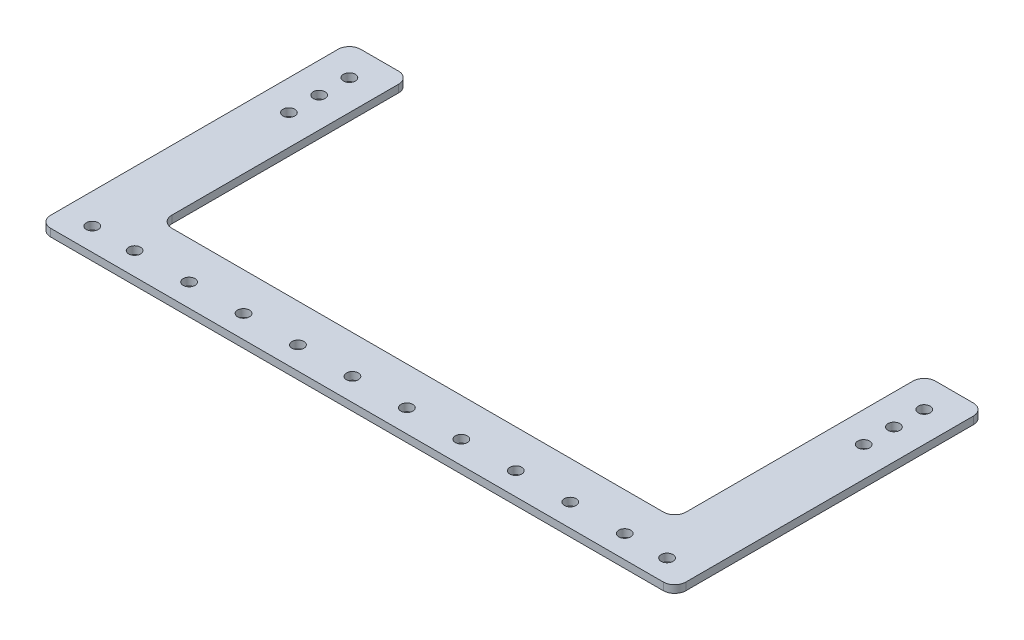
SolidWorks part; units mm, degrees
material "6061-T6 (SS)"
ref_plane "Front Plane" through (0, 0, 0) normal (0, 0, 1) x (1, 0, 0)
ref_plane "Top Plane" through (0, 0, 0) normal (0, 1, 0) x (1, 0, 0)
ref_plane "Right Plane" through (0, 0, 0) normal (1, 0, 0) x (0, 0, -1)
sketch "Sketch2" plane through (0, 0, 0) normal (0, 1, 0) x (1, 0, 0)
  line L0 (0, 65.0875) -> (0, -65.0875) construction
  line L1 (-133.35, -65.0875) -> (133.35, -65.0875)
  line L2 (-133.35, -65.0875) -> (-133.35, 65.0875)
  line L3 (-133.35, 65.0875) -> (133.35, 65.0875)
  line L4 (133.35, -65.0875) -> (133.35, 65.0875)
  line L5 (-133.35, -65.0875) -> (133.35, 65.0875) construction
  line L6 (-133.35, 65.0875) -> (133.35, -65.0875) construction
  line L7 (-107.95, 65.0875) -> (107.95, 65.0875)
  line L8 (-107.95, 65.0875) -> (-107.95, -39.624)
  line L9 (-107.95, -39.624) -> (107.95, -39.624)
  line L10 (107.95, 65.0875) -> (107.95, -39.624)
  line L11 (133.35, 65.0875) -> (107.95, 65.0875) construction
  line L12 (133.35, 65.0875) -> (133.35, -39.624) construction
  line L13 (133.35, -39.624) -> (107.95, -39.624) construction
  line L14 (107.95, 65.0875) -> (107.95, -39.624) construction
  circle A0 centre (-120.65, 52.3875) radius 2.4892
  circle A1 centre (-120.65, 39.6875) radius 2.4892
  circle A2 centre (-120.65, 26.9875) radius 2.4892
  circle A6 centre (120.65, 26.9875) radius 2.4892
  circle A7 centre (120.65, 39.6875) radius 2.4892
  circle A8 centre (120.65, 52.3875) radius 2.4892
  point P0 (0, 0)
  point P10 (0, -39.624)
  point P11 (0, -65.0875)
  dimension "D8" = 4.9784
  dimension "D1" = 266.7
  dimension "D2" = 130.175
  dimension "D3" = 215.9
  dimension "D4" = 25.4635
  dimension "D5" = 12.7
  dimension "D6" = 12.7
  dimension "D7" = 12.7
  dimension "D9" = 12.7
  dimension "D10" = 12.7
  dimension "D11" = 12.7
extrude "Boss-Extrude1" add sketch "Sketch2" along normal blind 3.175 contours L3 L10 L9 L8 L2 L1 L4 A7 A0 A1 A2 A6 A8 region at (-130.3823, 0, 0)
fillet "Fillet1" radius 4.7625 8 edges at (133.35, 1.5875, -65.0875) (-133.35, 1.5875, 65.0875) (-133.35, 1.5875, -65.0875) (-107.95, 1.5875, -65.0875) (-107.95, 1.5875, 39.624) (107.95, 1.5875, 39.624) (107.95, 1.5875, -65.0875) (133.35, 1.5875, 65.0875)
sketch "Sketch3" plane through (0, 3.175, 0) normal (0, 1, 0) x (1, 0, 0)
  line L0 (-133.35, -60.325) -> (-133.35, 60.325) construction
  line L1 (-128.5875, -65.0875) -> (128.5875, -65.0875) construction
  line L2 (102.87, -55.5625) -> (120.65, -55.5625) construction
  line L3 (-103.1875, -39.624) -> (103.1875, -39.624) construction
  line L4 (-44.45, -39.624) -> (-44.45, -65.0875) construction
  line L5 (-120.65, -55.5625) -> (-102.87, -55.5625) construction
  line L7 (-107.95, -39.624) -> (107.95, -39.624) construction
  line L8 (-48.4188, -39.624) -> (-40.4813, -39.624) construction
  line L9 (-48.4188, -39.624) -> (-48.4188, -65.0875) construction
  line L10 (-48.4188, -65.0875) -> (-40.4813, -65.0875) construction
  line L11 (-40.4813, -39.624) -> (-40.4813, -65.0875) construction
  line L12 (-133.35, -65.0875) -> (133.35, -65.0875) construction
  circle A38 centre (-102.87, -55.5625) radius 2.4892
  circle A40 centre (-80.01, -55.5625) radius 2.4892
  circle A41 centre (-120.65, -55.5625) radius 2.4892
  circle A55 centre (-57.15, -55.5625) radius 2.4892
  circle A63 centre (120.65, -55.5625) radius 2.4892
  circle A64 centre (-120.65, 26.9875) radius 2.4892 construction
  circle A65 centre (-34.29, -55.5625) radius 2.4892
  circle A66 centre (-11.43, -55.5625) radius 2.4892
  circle A67 centre (11.43, -55.5625) radius 2.4892
  circle A68 centre (34.29, -55.5625) radius 2.4892
  circle A69 centre (57.15, -55.5625) radius 2.4892
  circle A74 centre (80.01, -55.5625) radius 2.4892
  circle A75 centre (102.87, -55.5625) radius 2.4892
  point P48 (-44.45, -39.624)
  dimension "D1" = 22.86
  dimension "D6" = 88.9
  dimension "D2" = 12.7
  dimension "D3" = 9.525
  dimension "D4" = 10
  dimension "D7" = 7.9375
extrude "Cut-Extrude1" cut sketch "Sketch3" against normal through all
